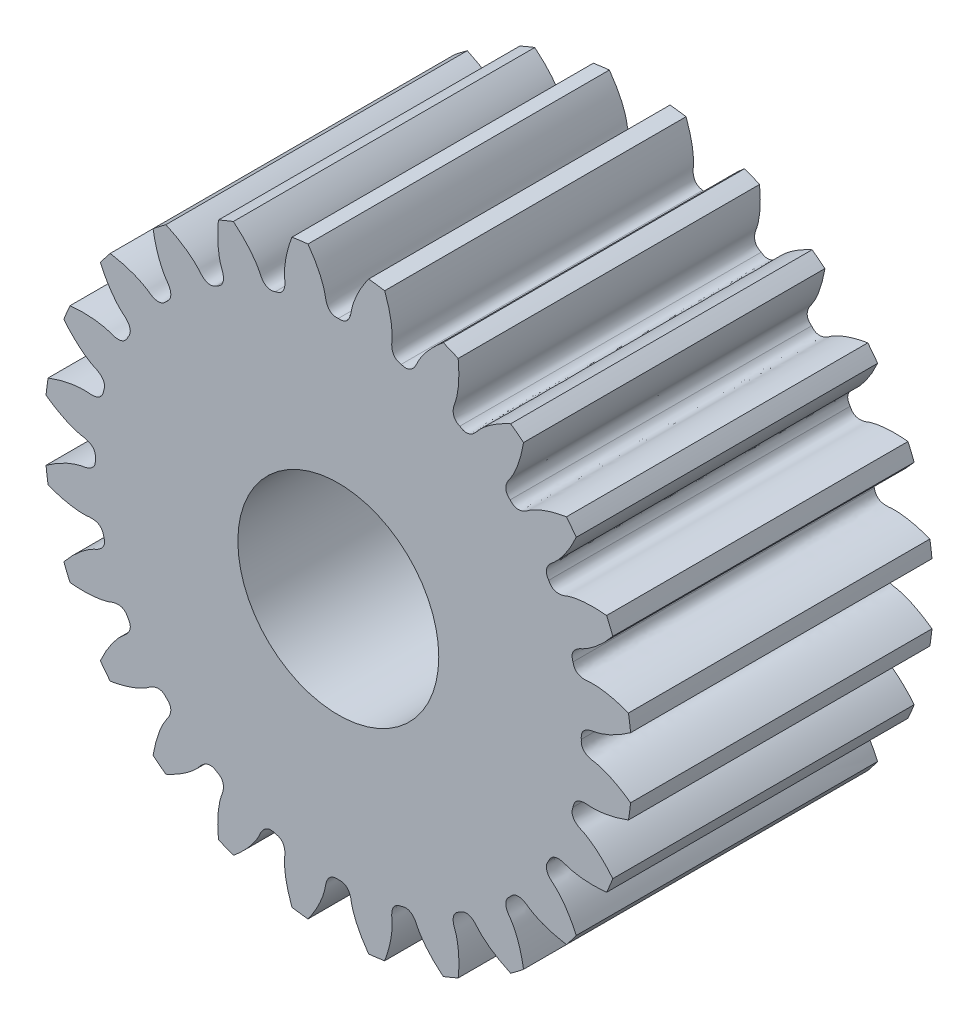
SolidWorks part; units mm, degrees
ref_plane "Front Plane" through (0, 0, 0) normal (0, 0, 1) x (1, 0, 0)
ref_plane "Top Plane" through (0, 0, 0) normal (0, 1, 0) x (1, 0, 0)
ref_plane "Right Plane" through (0, 0, 0) normal (1, 0, 0) x (0, 0, -1)
ref_axis "Axis1" through (0, 0, -88.99) along (0, 0, 1)
sketch "Gear-BaseSketch" plane through (0, 0, 0) normal (0, 0, 1) x (1, 0, 0)
  circle A0 centre (0, 0) radius 5.85
  dimension "D1" = 11.7
extrude "0.45 Module, 10.8000mm P.D." add sketch "Gear-BaseSketch" along normal mid plane 6
sketch "Tooth-Sketch; Backlash: 0.0000mm" plane through (0, 0, 0) normal (0, 0, 1) x (1, 0, 0)
  line L0 (0, 0) -> (0, 7.6115) construction
  arc A0 (-0.6676, 5.9042) -> (0.6676, 5.9042) centre (0, 0) cw
  spline S0 degree 3 poles (-0.6676, 5.9042) (-0.6197, 5.8425) (-0.5538, 5.7506) (-0.4768, 5.6275) (-0.4291, 5.5439) (-0.3887, 5.4659) (-0.355, 5.3938) (-0.3275, 5.3282) (-0.3056, 5.2694) (-0.2887, 5.2176) (-0.2761, 5.1733) (-0.2674, 5.1367) (-0.2612, 5.1062) (-0.258, 5.0834) (-0.2551, 5.0661) (-0.2526, 5.0532) (-0.2481, 5.0326) (-0.2405, 5.0047) (-0.2278, 4.9703) (-0.2113, 4.9373) (-0.1894, 4.9053) (-0.1592, 4.8747) (-0.0989, 4.8367) (-0.0391, 4.8344) (0, 4.8373) knots 0 0 0 0 0.176474 0.255257 0.327737 0.393915 0.45379 0.507362 0.554632 0.595599 0.630264 0.658625 0.680685 0.700525 0.710566 0.72042 0.730103 0.758269 0.785574 0.812849 0.841358 0.872902 0.909457 1 1 1 1
  spline S1 degree 3 poles (0.6676, 5.9042) (0.6197, 5.8425) (0.5538, 5.7506) (0.4768, 5.6275) (0.4291, 5.5439) (0.3887, 5.4659) (0.355, 5.3938) (0.3275, 5.3282) (0.3056, 5.2694) (0.2887, 5.2176) (0.2761, 5.1733) (0.2674, 5.1367) (0.2612, 5.1062) (0.258, 5.0834) (0.2551, 5.0661) (0.2526, 5.0532) (0.2481, 5.0326) (0.2405, 5.0047) (0.2278, 4.9703) (0.2113, 4.9373) (0.1894, 4.9053) (0.1592, 4.8747) (0.0989, 4.8367) (0.0391, 4.8344) (0, 4.8373) knots 0 0 0 0 0.176474 0.255257 0.327737 0.393915 0.45379 0.507362 0.554632 0.595599 0.630264 0.658625 0.680685 0.700525 0.710566 0.72042 0.730103 0.758269 0.785574 0.812849 0.841358 0.872902 0.909457 1 1 1 1
extrude "Tooth-Cut, Coarse Pitch Involute 20 deg" cut sketch "Tooth-Sketch; Backlash: 0.0000mm" against normal through all and the other way through all
pattern_circular "Tooth Pattern, 24 / 24" count 24 every 15 about axis through (0, 0, -88.99) along (0, 0, 1) of "Tooth-Cut, Coarse Pitch Involute 20 deg"
hole_wizard "Ø4.0 (4) Diameter Hole1" positions "Sketch4" profile "Sketch3" hole size "Ø4.0" standard "DIN" end condition through all
sketch "Sketch4" plane through (0, 0, 3) normal (0, 0, 1) x (1, 0, 0)
  point P0 (0, 0)
sketch "Sketch3" plane through (0, 0, 3) normal (1, 0, 0) x (0, -1, 0)
  line L0 (0, 0) -> (0, 6)
  line L1 (0, 6) -> (2, 6)
  line L2 (2, 6) -> (2, 0)
  line L5 (2, 0) -> (0, 0)
  line L11 (0, -6.35) -> (0, 107.95) construction
  dimension "Thru Hole Dia." = 4
  dimension "Thru Hole Depth" = 6
scale "Echelle1" scale about centroid uniform scaling yes scale factor 2
scale "Echelle2" scale about centroid uniform scaling yes scale factor 0.25
